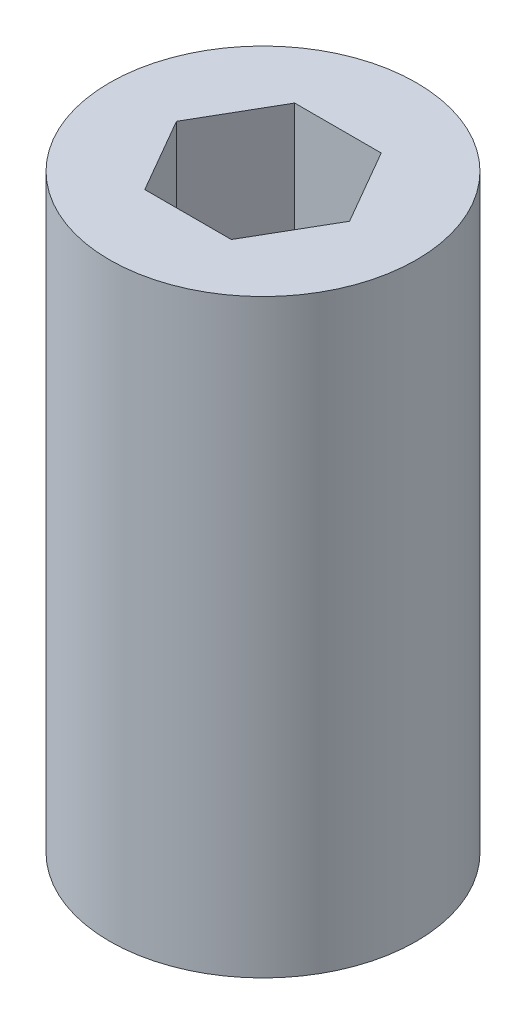
SolidWorks part; units mm, degrees
ref_plane "Front Plane" through (0, 0, 0) normal (0, 0, 1) x (1, 0, 0)
ref_plane "Top Plane" through (0, 0, 0) normal (0, 1, 0) x (1, 0, 0)
ref_plane "Right Plane" through (0, 0, 0) normal (1, 0, 0) x (0, 0, -1)
sketch "Sketch1" plane through (0, 0, 0) normal (0, 1, 0) x (1, 0, 0)
  line L1 (7.3323, 0) -> (3.6662, 6.35)
  line L2 (3.6662, 6.35) -> (-3.6662, 6.35)
  line L3 (-3.6662, 6.35) -> (-7.3323, 0)
  line L4 (-7.3323, 0) -> (-3.6662, -6.35)
  line L5 (-3.6662, -6.35) -> (3.6662, -6.35)
  line L6 (3.6662, -6.35) -> (7.3323, 0)
  circle A0 centre (0, 0) radius 13
  circle A1 centre (0, 0) radius 6.35 construction
  dimension "D2" = 26
  dimension "D1" = 12.7
extrude "Boss-Extrude1" add sketch "Sketch1" along normal blind 30
sketch "Sketch2" plane through (0, 0, 0) normal (0, -1, 0) x (1, 0, 0)
  circle A0 centre (0, 0) radius 13
  dimension "D1" = 26
extrude "Boss-Extrude2" add sketch "Sketch2" along normal blind 20
sketch "Sketch3" plane through (0, -20, 0) normal (0, -1, 0) x (1, 0, 0)
  arc A57 (-5.5304, 4.7688) -> (-8.3889, 5.7316) centre (-9.671, -2.7995) ccw
  arc A58 (-4.9617, 5.358) -> (-5.5304, 4.7688) centre (0, 0) ccw
  arc A59 (-6.0251, 8.1807) -> (-4.9617, 5.358) centre (2.4553, 9.7641) ccw
  arc A60 (-5.0713, 8.8038) -> (-6.0251, 8.1807) centre (0, 0) ccw
  arc A61 (-2.9136, 6.6961) -> (-5.0713, 8.8038) centre (-9.9279, 1.6738) ccw
  arc A62 (-2.1455, 6.9802) -> (-2.9136, 6.6961) centre (0, 0) ccw
  arc A63 (-1.879, 9.9847) -> (-2.1455, 6.9802) centre (6.4486, 7.7318) ccw
  arc A64 (-0.7492, 10.1323) -> (-1.879, 9.9847) centre (0, 0) ccw
  arc A65 (0.2803, 7.2971) -> (-0.7492, 10.1323) centre (-8.2185, 5.8156) ccw
  arc A66 (1.0955, 7.2199) -> (0.2803, 7.2971) centre (0, 0) ccw
  arc A67 (2.6393, 9.8112) -> (1.0955, 7.2199) centre (9.1647, 4.1682) ccw
  arc A68 (3.7212, 9.454) -> (2.6393, 9.8112) centre (0, 0) ccw
  arc A69 (3.4186, 6.4529) -> (3.7212, 9.454) centre (-4.8813, 8.8056) ccw
  arc A70 (4.1196, 6.0295) -> (3.4186, 6.4529) centre (0, 0) ccw
  arc A71 (6.6349, 7.6944) -> (4.1196, 6.0295) centre (10.0656, -0.221) ccw
  arc A72 (7.4546, 6.9032) -> (6.6349, 7.6944) centre (0, 0) ccw
  arc A73 (5.8799, 4.3306) -> (7.4546, 6.9032) centre (-0.5773, 10.0515) ccw
  arc A74 (6.3278, 3.645) -> (5.8799, 4.3306) centre (0, 0) ccw
  arc A75 (9.3163, 4.0537) -> (6.3278, 3.645) centre (8.9729, -4.5664) ccw
  arc A76 (9.7116, 2.9851) -> (9.3163, 4.0537) centre (0, 0) ccw
  arc A77 (7.1765, 1.3505) -> (9.7116, 2.9851) centre (3.841, 9.3066) ccw
  arc A78 (7.2826, 0.5385) -> (7.1765, 1.3505) centre (0, 0) ccw
  arc A79 (10.1525, -0.3899) -> (7.2826, 0.5385) centre (6.103, -8.0074) ccw
  arc A80 (10.045, -1.5242) -> (10.1525, -0.3899) centre (0, 0) ccw
  arc A81 (7.0518, -1.897) -> (10.045, -1.5242) centre (7.4986, 6.7184) ccw
  arc A82 (6.7951, -2.6746) -> (7.0518, -1.897) centre (0, 0) ccw
  arc A83 (8.9779, -4.7563) -> (6.7951, -2.6746) centre (2.0244, -9.8624) ccw
  arc A84 (8.3889, -5.7316) -> (8.9779, -4.7563) centre (0, 0) ccw
  arc A85 (5.5304, -4.7688) -> (8.3889, -5.7316) centre (9.671, 2.7995) ccw
  arc A86 (4.9617, -5.358) -> (5.5304, -4.7688) centre (0, 0) ccw
  arc A87 (6.0251, -8.1807) -> (4.9617, -5.358) centre (-2.4553, -9.7641) ccw
  arc A88 (5.0713, -8.8038) -> (6.0251, -8.1807) centre (0, 0) ccw
  arc A89 (2.9136, -6.6961) -> (5.0713, -8.8038) centre (9.9279, -1.6738) ccw
  arc A90 (2.1455, -6.9802) -> (2.9136, -6.6961) centre (0, 0) ccw
  arc A91 (1.879, -9.9847) -> (2.1455, -6.9802) centre (-6.4486, -7.7318) ccw
  arc A92 (0.7492, -10.1323) -> (1.879, -9.9847) centre (0, 0) ccw
  arc A93 (-0.2803, -7.2971) -> (0.7492, -10.1323) centre (8.2185, -5.8156) ccw
  arc A94 (-1.0955, -7.2199) -> (-0.2803, -7.2971) centre (0, 0) ccw
  arc A95 (-2.6393, -9.8112) -> (-1.0955, -7.2199) centre (-9.1647, -4.1682) ccw
  arc A96 (-3.7212, -9.454) -> (-2.6393, -9.8112) centre (0, 0) ccw
  arc A97 (-3.4186, -6.4529) -> (-3.7212, -9.454) centre (4.8813, -8.8056) ccw
  arc A98 (-4.1196, -6.0295) -> (-3.4186, -6.4529) centre (0, 0) ccw
  arc A99 (-6.6349, -7.6944) -> (-4.1196, -6.0295) centre (-10.0656, 0.221) ccw
  arc A100 (-7.4546, -6.9032) -> (-6.6349, -7.6944) centre (0, 0) ccw
  arc A101 (-5.8799, -4.3306) -> (-7.4546, -6.9032) centre (0.5773, -10.0515) ccw
  arc A102 (-6.3278, -3.645) -> (-5.8799, -4.3306) centre (0, 0) ccw
  arc A103 (-9.3163, -4.0537) -> (-6.3278, -3.645) centre (-8.9729, 4.5664) ccw
  arc A104 (-9.7116, -2.9851) -> (-9.3163, -4.0537) centre (0, 0) ccw
  arc A105 (-7.1765, -1.3505) -> (-9.7116, -2.9851) centre (-3.841, -9.3066) ccw
  arc A106 (-7.2826, -0.5385) -> (-7.1765, -1.3505) centre (0, 0) ccw
  arc A107 (-10.1525, 0.3899) -> (-7.2826, -0.5385) centre (-6.103, 8.0074) ccw
  arc A108 (-10.045, 1.5242) -> (-10.1525, 0.3899) centre (0, 0) ccw
  arc A109 (-7.0518, 1.897) -> (-10.045, 1.5242) centre (-7.4986, -6.7184) ccw
  arc A110 (-6.7951, 2.6746) -> (-7.0518, 1.897) centre (0, 0) ccw
  arc A111 (-8.9779, 4.7563) -> (-6.7951, 2.6746) centre (-2.0244, 9.8624) ccw
  arc A112 (-8.3889, 5.7316) -> (-8.9779, 4.7563) centre (0, 0) ccw
  arc A113 (-5.5304, 4.7688) -> (-8.3889, 5.7316) centre (-9.671, -2.7995) ccw
  arc A114 (-4.9617, 5.358) -> (-5.5304, 4.7688) centre (0, 0) ccw
  arc A115 (-6.0251, 8.1807) -> (-4.9617, 5.358) centre (2.4553, 9.7641) ccw
  arc A116 (-5.0713, 8.8038) -> (-6.0251, 8.1807) centre (0, 0) ccw
  arc A117 (-2.9136, 6.6961) -> (-5.0713, 8.8038) centre (-9.9279, 1.6738) ccw
  arc A118 (-2.1455, 6.9802) -> (-2.9136, 6.6961) centre (0, 0) ccw
  arc A119 (-1.879, 9.9847) -> (-2.1455, 6.9802) centre (6.4486, 7.7318) ccw
  arc A120 (-0.7492, 10.1323) -> (-1.879, 9.9847) centre (0, 0) ccw
  arc A121 (0.2803, 7.2971) -> (-0.7492, 10.1323) centre (-8.2185, 5.8156) ccw
  arc A122 (1.0955, 7.2199) -> (0.2803, 7.2971) centre (0, 0) ccw
  arc A123 (2.6393, 9.8112) -> (1.0955, 7.2199) centre (9.1647, 4.1682) ccw
  arc A124 (3.7212, 9.454) -> (2.6393, 9.8112) centre (0, 0) ccw
  arc A125 (3.4186, 6.4529) -> (3.7212, 9.454) centre (-4.8813, 8.8056) ccw
  arc A126 (4.1196, 6.0295) -> (3.4186, 6.4529) centre (0, 0) ccw
  arc A127 (6.6349, 7.6944) -> (4.1196, 6.0295) centre (10.0656, -0.221) ccw
  arc A128 (7.4546, 6.9032) -> (6.6349, 7.6944) centre (0, 0) ccw
  arc A129 (5.8799, 4.3306) -> (7.4546, 6.9032) centre (-0.5773, 10.0515) ccw
  arc A130 (6.3278, 3.645) -> (5.8799, 4.3306) centre (0, 0) ccw
  arc A131 (9.3163, 4.0537) -> (6.3278, 3.645) centre (8.9729, -4.5664) ccw
  arc A132 (9.7116, 2.9851) -> (9.3163, 4.0537) centre (0, 0) ccw
  arc A133 (7.1765, 1.3505) -> (9.7116, 2.9851) centre (3.841, 9.3066) ccw
  arc A134 (7.2826, 0.5385) -> (7.1765, 1.3505) centre (0, 0) ccw
  arc A135 (10.1525, -0.3899) -> (7.2826, 0.5385) centre (6.103, -8.0074) ccw
  arc A136 (10.045, -1.5242) -> (10.1525, -0.3899) centre (0, 0) ccw
  arc A137 (7.0518, -1.897) -> (10.045, -1.5242) centre (7.4986, 6.7184) ccw
  arc A138 (6.7951, -2.6746) -> (7.0518, -1.897) centre (0, 0) ccw
  arc A139 (8.9779, -4.7563) -> (6.7951, -2.6746) centre (2.0244, -9.8624) ccw
  arc A140 (8.3889, -5.7316) -> (8.9779, -4.7563) centre (0, 0) ccw
  arc A141 (5.5304, -4.7688) -> (8.3889, -5.7316) centre (9.671, 2.7995) ccw
  arc A142 (4.9617, -5.358) -> (5.5304, -4.7688) centre (0, 0) ccw
  arc A143 (6.0251, -8.1807) -> (4.9617, -5.358) centre (-2.4553, -9.7641) ccw
  arc A144 (5.0713, -8.8038) -> (6.0251, -8.1807) centre (0, 0) ccw
  arc A145 (2.9136, -6.6961) -> (5.0713, -8.8038) centre (9.9279, -1.6738) ccw
  arc A146 (2.1455, -6.9802) -> (2.9136, -6.6961) centre (0, 0) ccw
  arc A147 (1.879, -9.9847) -> (2.1455, -6.9802) centre (-6.4486, -7.7318) ccw
  arc A148 (0.7492, -10.1323) -> (1.879, -9.9847) centre (0, 0) ccw
  arc A149 (-0.2803, -7.2971) -> (0.7492, -10.1323) centre (8.2185, -5.8156) ccw
  arc A150 (-1.0955, -7.2199) -> (-0.2803, -7.2971) centre (0, 0) ccw
  arc A151 (-2.6393, -9.8112) -> (-1.0955, -7.2199) centre (-9.1647, -4.1682) ccw
  arc A152 (-3.7212, -9.454) -> (-2.6393, -9.8112) centre (0, 0) ccw
  arc A153 (-3.4186, -6.4529) -> (-3.7212, -9.454) centre (4.8813, -8.8056) ccw
  arc A154 (-4.1196, -6.0295) -> (-3.4186, -6.4529) centre (0, 0) ccw
  arc A155 (-6.6349, -7.6944) -> (-4.1196, -6.0295) centre (-10.0656, 0.221) ccw
  arc A156 (-7.4546, -6.9032) -> (-6.6349, -7.6944) centre (0, 0) ccw
  arc A157 (-5.8799, -4.3306) -> (-7.4546, -6.9032) centre (0.5773, -10.0515) ccw
  arc A158 (-6.3278, -3.645) -> (-5.8799, -4.3306) centre (0, 0) ccw
  arc A159 (-9.3163, -4.0537) -> (-6.3278, -3.645) centre (-8.9729, 4.5664) ccw
  arc A160 (-9.7116, -2.9851) -> (-9.3163, -4.0537) centre (0, 0) ccw
  arc A161 (-7.1765, -1.3505) -> (-9.7116, -2.9851) centre (-3.841, -9.3066) ccw
  arc A162 (-7.2826, -0.5385) -> (-7.1765, -1.3505) centre (0, 0) ccw
  arc A163 (-10.1525, 0.3899) -> (-7.2826, -0.5385) centre (-6.103, 8.0074) ccw
  arc A164 (-10.045, 1.5242) -> (-10.1525, 0.3899) centre (0, 0) ccw
  arc A165 (-7.0518, 1.897) -> (-10.045, 1.5242) centre (-7.4986, -6.7184) ccw
  arc A166 (-6.7951, 2.6746) -> (-7.0518, 1.897) centre (0, 0) ccw
  arc A167 (-8.9779, 4.7563) -> (-6.7951, 2.6746) centre (-2.0244, 9.8624) ccw
  arc A168 (-8.3889, 5.7316) -> (-8.9779, 4.7563) centre (0, 0) ccw
  dimension "D1" = 0
extrude "Cut-Extrude1" cut sketch "Sketch3" against normal blind 21
